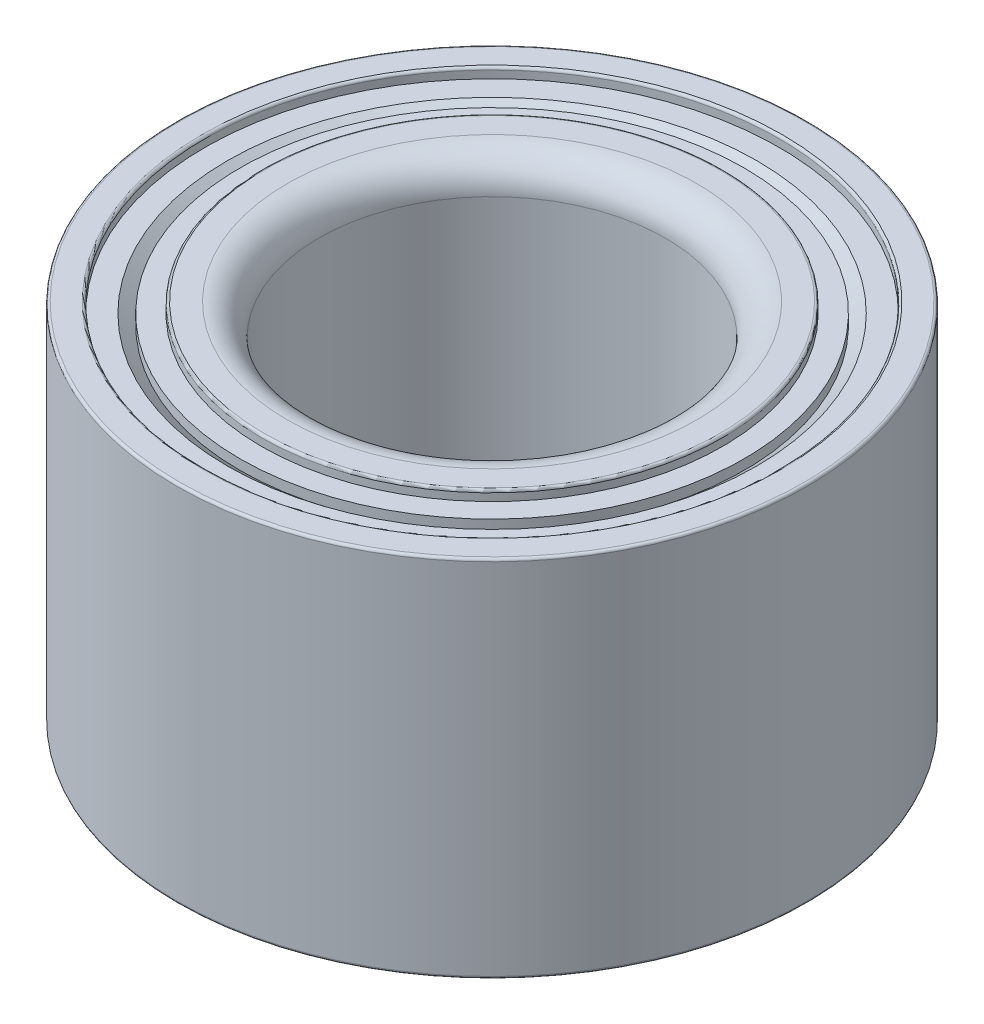
SolidWorks part; units mm, degrees
material "Stainless Steel (ferritic)"
ref_plane "Front Plane" through (0, 0, 0) normal (0, 0, 1) x (1, 0, 0)
ref_plane "Top Plane" through (0, 0, 0) normal (0, 1, 0) x (1, 0, 0)
ref_plane "Right Plane" through (0, 0, 0) normal (1, 0, 0) x (0, 0, -1)
sketch "Sketch1" plane through (0, 0, 0) normal (0, 1, 0) x (1, 0, 0)
  circle A0 centre (0, 0) radius 31.75
  circle A1 centre (0, 0) radius 17.4625
  dimension "D1" = 63.5
  dimension "D2" = 34.925
extrude "Boss-Extrude1" add sketch "Sketch1" along normal blind 18.3515 and the other way blind 18.3515
sketch "Sketch2" plane through (0, 18.3515, 0) normal (0, 1, 0) x (1, 0, 0)
  circle A1 centre (0, 0) radius 23.241
  circle A2 centre (0, 0) radius 28.956
  circle A3 centre (0, 0) radius 28.956
  dimension "D1" = 2.794
  dimension "D2" = 5.715
extrude "Cut-Extrude1" cut sketch "Sketch2" against normal blind 1.016
mirror "Mirror1" about plane through (0, 0, 0) normal (0, 1, 0) of "Cut-Extrude1"
sketch "Sketch3" plane through (0, -17.3355, 0) normal (0, -1, 0) x (1, 0, 0)
  circle A2 centre (0, 0) radius 26.67
  circle A4 centre (0, 0) radius 25.4
  dimension "D1" = 50.8
  dimension "D2" = 1.27
extrude "Cut-Extrude2" cut sketch "Sketch3" against normal blind 1.016
fillet "Fillet1" radius 3.175 2 edges at (0, -18.3515, 17.4625) (0, 18.3515, 17.4625)
mirror "Mirror4" about plane through (0, 0, 0) normal (0, 1, 0) of "Cut-Extrude2"
sketch "Sketch4" plane through (0, 0, 0) normal (1, 0, 0) x (0, 0, -1)
  line L0 (-25.4, 16.3195) -> (-26.67, 17.3355)
  line L1 (26.67, 16.3195) -> (-26.67, 16.3195) construction
  line L2 (25.4, 16.3195) -> (-25.4, 16.3195) construction
  line L3 (26.67, 17.3355) -> (-26.67, 17.3355) construction
  line L4 (28.956, 17.3355) -> (-28.956, 17.3355) construction
  line L5 (-26.67, 17.3355) -> (-26.67, 16.3195)
  line L6 (-26.67, 16.3195) -> (-25.4, 16.3195)
  line L7 (0, 0) -> (0, 17.3355) construction
revolve "Revolve1" add sketch "Sketch4" angle 360 about L7
mirror "Mirror5" about plane through (0, 0, 0) normal (0, 1, 0) of "Revolve1"
fillet "Fillet2" radius 0.254 6 edges at (0, -18.3515, 28.956) (0, -18.3515, 31.75) (0, 18.3515, 28.956) (0, 18.3515, 31.75) (0, 18.3515, 23.241) (0, -18.3515, 23.241)
